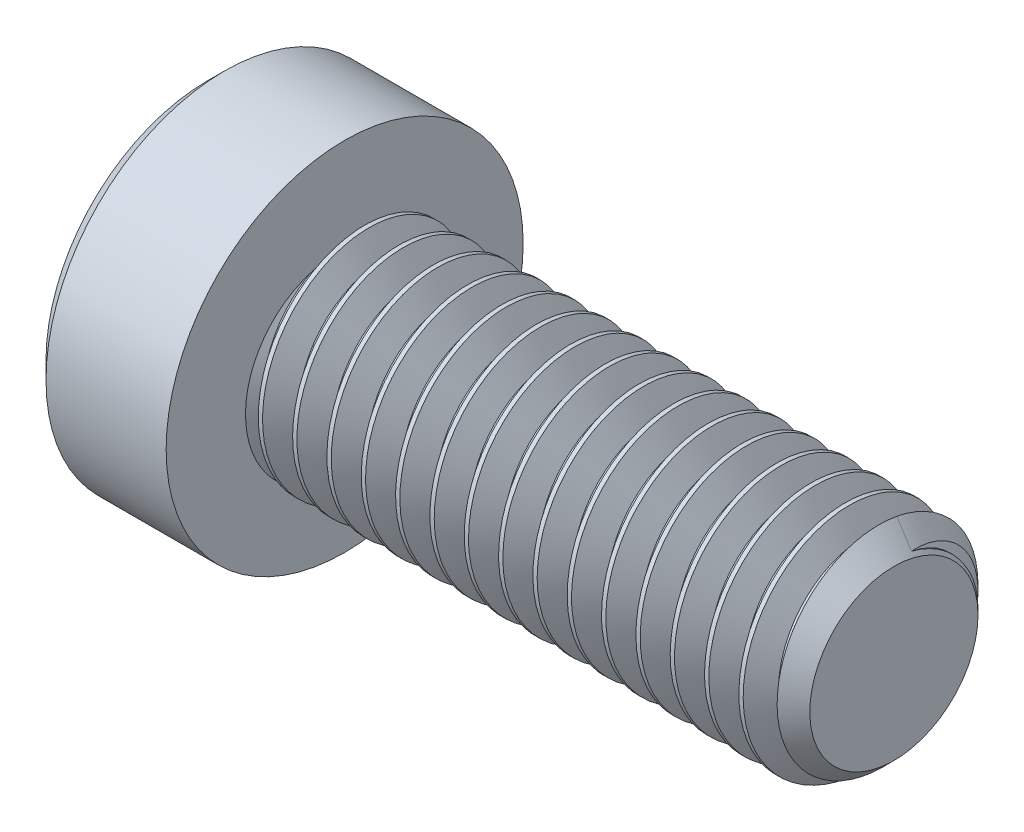
SolidWorks part; units mm, degrees
ref_plane "Front Plane" through (0, 0, 0) normal (0, 0, 1) x (1, 0, 0)
ref_plane "Top Plane" through (0, 0, 0) normal (0, 1, 0) x (1, 0, 0)
ref_plane "Right Plane" through (0, 0, 0) normal (1, 0, 0) x (0, 0, -1)
sketch "Sketch1" plane through (0, 0, 0) normal (0, 0, 1) x (1, 0, 0)
  line L0 (10, 0) -> (-10, 0) construction
  line L1 (10, 4) -> (10, -4) construction
  line L2 (-10, 6.5) -> (-10, -6.5) construction
  line L3 (-10, 6.5) -> (-14.375, 6.5) construction
  line L4 (-14.375, 6.5) -> (-15, 5.875) construction
  line L5 (-15, 5.875) -> (-15, -5.875) construction
  line L6 (-15, -5.875) -> (-14.375, -6.5) construction
  line L7 (-14.375, -6.5) -> (-10, -6.5) construction
  point P7 (-11.05, 0)
  point P12 (5, -4)
  dimension "D1" = 45
  dimension "Dec." = 8
  dimension "Length" = 20
  dimension "Head Dia" = 13
  dimension "Head Height" = 5
  dimension "Hex Depth" = 3.95
  dimension "Chamfer" = 0.625
  dimension "D2" = 5
ref_plane "Plane1" through (10, 0, 0) normal (1, 0, 0) x (0, 0, -1)
ref_plane "Plane2" through (-15, 0, 0) normal (1, 0, 0) x (0, 0, -1)
sketch "Sketch2" plane through (10, 0, 0) normal (1, 0, 0) x (0, 0, -1)
  circle A0 centre (0, 0) radius 4
extrude "Boss-Extrude1" add sketch "Sketch2" against normal up to vertex (20 mm away) up to point (-10, 0, 0)
sketch "Sketch3" plane through (10, 0, 0) normal (1, 0, 0) x (0, 0, -1)
  circle A0 centre (0, 0) radius 4 construction
  circle A1 centre (0, 0) radius 4
curve "Helix/Spiral1" pitch 1.25 height 21.25 radius 4 centre (10, 0, 0) axis (-1, 0, 0) start towards (0, 1, 0) parameters "Pitch"=1.25
chamfer "Chamfer1" distance 0.9375 angle 45 1 edges at (10, 0, -4)
sketch "Sketch5" plane through (0, 0, 0) normal (0, 0, 1) x (1, 0, 0)
  line L0 (9.4531, 4) -> (10.5469, 4)
  line L1 (10.5469, 4) -> (10.0781, 3.1881)
  line L2 (10.0781, 3.1881) -> (9.9219, 3.1881)
  line L3 (9.9219, 3.1881) -> (9.4531, 4)
  line L4 (10, 3.1881) -> (10, 4) construction
  line L5 (9.6875, 3.5941) -> (10.3125, 3.5941) construction
  dimension "D1" = 60
  dimension "D2" = 0.625
  dimension "D3" = 0.1562
sweep "Cut-Sweep1" cut profiles "Sketch5" path "Helix/Spiral1" align with end faces yes
sketch "Sketch4" plane through (-15, 0, 0) normal (1, 0, 0) x (0, 0, -1)
  line L0 (-6.5, 0.7937) -> (6.5, 0.7937) construction
  line L1 (0, 2.8868) -> (-2.5, 1.4434)
  line L2 (-2.5, 1.4434) -> (-2.5, -1.4434)
  line L3 (-2.5, -1.4434) -> (0, -2.8868)
  line L4 (0, -2.8868) -> (2.5, -1.4434)
  line L5 (2.5, -1.4434) -> (2.5, 1.4434)
  line L6 (2.5, 1.4434) -> (0, 2.8868)
  line L7 (0, 0) -> (0, 0.7937) construction
  circle A0 centre (0, 0) radius 2.5 construction
  dimension "Hex Size" = 5
  dimension "D1" = 13
  dimension "D2" = 0.7937
sketch "Sketch6" plane through (0, 0, 0) normal (0, 0, 1) x (1, 0, 0)
  line L0 (-14.375, 6.5) -> (-15, 5.875) construction
  line L1 (-10, 6.5) -> (-14.375, 6.5) construction
  line L2 (-10, 6.5) -> (-10, -6.5) construction
  line L3 (-15, 5.875) -> (-15, -5.875) construction
  line L4 (-14.375, 6.5) -> (-15, 5.875)
  line L5 (-10, 6.5) -> (-14.375, 6.5)
  line L6 (-10, 6.5) -> (-10, 0)
  line L7 (-15, 5.875) -> (-15, 0)
  line L8 (-10, 0) -> (-15, 0) construction
  line L9 (-10, 0) -> (-15, 0)
revolve "Revolve1" add sketch "Sketch6" angle 360 about L8
extrude "Cut-Extrude1" cut sketch "Sketch4" along normal up to vertex (3.95 mm away) up to point (-11.05, 0, 0)
sketch "Sketch8" plane through (-15, 0, 0) normal (-1, 0, 0) x (0, 0, 1)
  circle A1 centre (0, 0) radius 2.8868
extrude "Cut-Extrude2" cut sketch "Sketch8" against normal through all draft 45
equation "\"D3@Helix/Spiral1\" = \"Length@Sketch1\"+\"Pitch@Helix/Spiral1\""
equation "\"D3@Sketch5\" = \"Pitch@Helix/Spiral1\"*.125"
equation "\"D2@Sketch5\" = \"Pitch@Helix/Spiral1\"*.50"
equation "\"D1@Chamfer1\" = \"Pitch@Helix/Spiral1\"*.75"
equation "\"D2@Sketch1\" = \"Pitch@Helix/Spiral1\"*4"
equation "\"D1@Sketch4\" = \"Head Dia@Sketch1\""
equation "\"Chamfer@Sketch1\" = \"Head Height@Sketch1\"/8"
